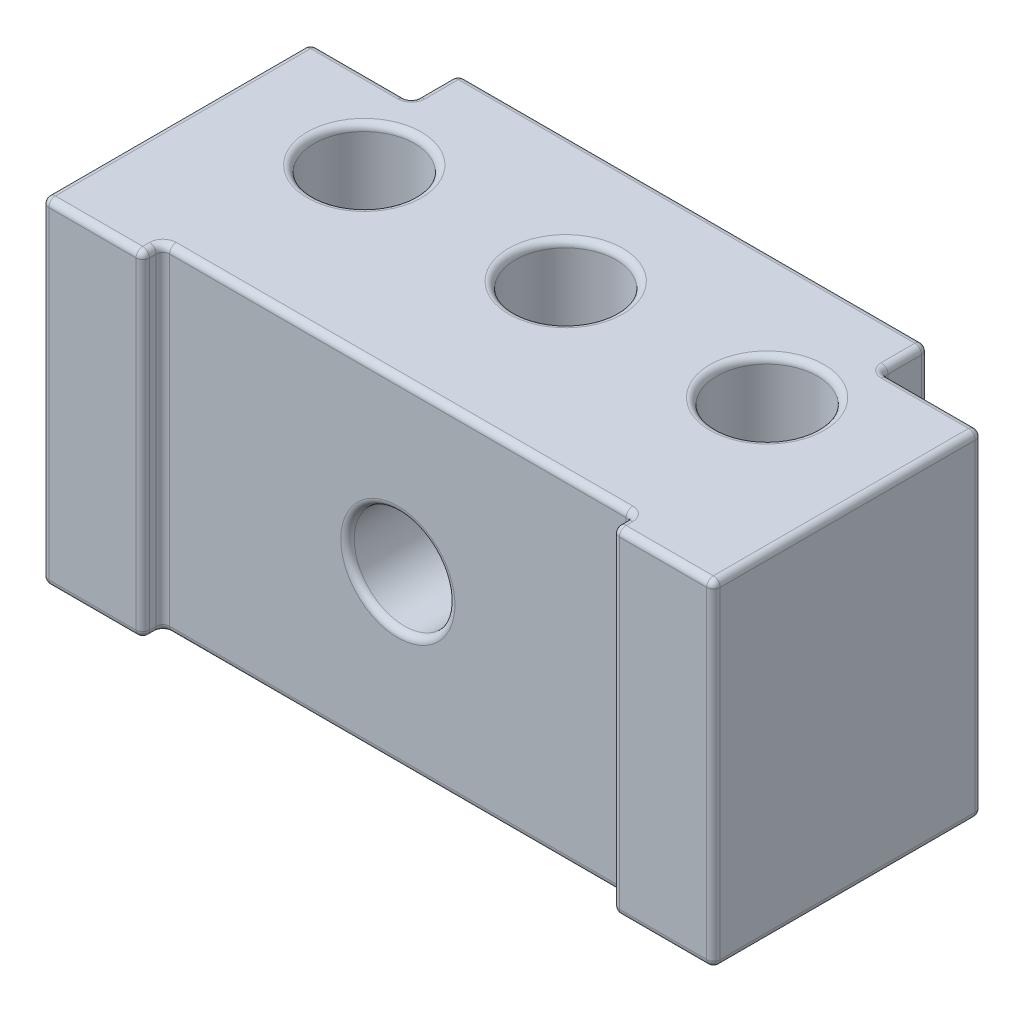
SolidWorks part; units mm, degrees
material "6061 Alloy"
ref_plane "Front Plane" through (0, 0, 0) normal (0, 0, 1) x (1, 0, 0)
ref_plane "Top Plane" through (0, 0, 0) normal (0, 1, 0) x (1, 0, 0)
ref_plane "Right Plane" through (0, 0, 0) normal (1, 0, 0) x (0, 0, -1)
sketch "Sketch1" plane through (0, 0, 0) normal (0, 1, 0) x (1, 0, 0)
  line L0 (0, 0) -> (30, 0)
  line L1 (30, 0) -> (30, 6)
  line L2 (30, 6) -> (170, 6)
  line L3 (170, 6) -> (170, 0)
  line L7 (170, 80) -> (170, 94)
  line L8 (0, 0) -> (0, 80)
  line L9 (0, 80) -> (30, 80)
  line L10 (30, 80) -> (30, 94)
  line L11 (30, 94) -> (170, 94)
  line L15 (170, 0) -> (200, 0)
  line L16 (200, 0) -> (200, 80)
  line L17 (200, 80) -> (170, 80)
  circle A0 centre (40, 56) radius 15
  circle A1 centre (100, 56) radius 15
  circle A2 centre (160, 56) radius 15
  dimension "D1" = 30
extrude "Boss-Extrude2" add sketch "Sketch1" along normal blind 100 contours L2 L3 L15 L16 L17 L7 L11 L10 L9 L8 L0 L1
extrude "Cut-Extrude5" cut sketch "Sketch1<9>" along normal blind 100 contours A2 | A1 | A0 region at (40, 0, -56) region at (100, 0, -56) region at (160, 0, -56)
sketch "Sketch1<9>" plane through (0, 0, 0) normal (0, 1, 0) x (1, 0, 0) same geometry as "Sketch1"
sketch "Sketch8" plane through (0, 0, -6) normal (0, 0, 1) x (1, 0, 0)
  circle A0 centre (100, 50) radius 15
hole_wizard "Ø1.0 (1) Diameter Hole1" positions "Sketch11" profile "Sketch10" hole size "Ø1.0" standard "ANSI Metric"
sketch "Sketch11" plane through (0, 0, -6) normal (0, 0, 1) x (1, 0, 0)
  point P0 (100, 50)
sketch "Sketch10" plane through (100, 50, -6) normal (1, 0, 0) x (0, -1, 0)
  line L0 (0, 0) -> (0, 59.0129)
  line L1 (0, 59.0129) -> (15, 50)
  line L2 (15, 50) -> (15, 0)
  line L5 (15, 0) -> (0, 0)
  line L10 (0, 59.0129) -> (-15, 50) construction
  line L11 (0, -6.35) -> (0, 107.95) construction
  dimension "Hole Dia." = 30
  dimension "Hole Depth" = 50
  dimension "Drill Angle" = 118
fillet "Fillet1" radius 2 43 edges at (170, 50, 0) (30, 50, 0) (115, 50, -6) (30, 50, -6) (170, 50, -6) (170, 50, -94) (200, 50, 0) (40, 0, -41) (100, 0, -41) (160, 0, -41) (100, 0, -6) (170, 0, -3) (185, 0, 0) (200, 0, -40) (170, 0, -87) (100, 0, -94) (15, 0, 0) (30, 0, -3) (200, 50, -80) (170, 50, -80) (185, 0, -80) (30, 50, -94) (30, 0, -87) (15, 100, 0) (30, 100, -87) (100, 100, -94) (170, 100, -87) (185, 100, -80) (200, 100, -40) (185, 100, 0) (170, 100, -3) (100, 100, -6) (30, 100, -3) (40, 100, -41) (100, 100, -41) (160, 100, -41) (30, 50, -80) (15, 100, -80) (15, 0, -80) (0, 50, -80) (0, 100, -40) (0, 50, 0) (0, 0, -40)
